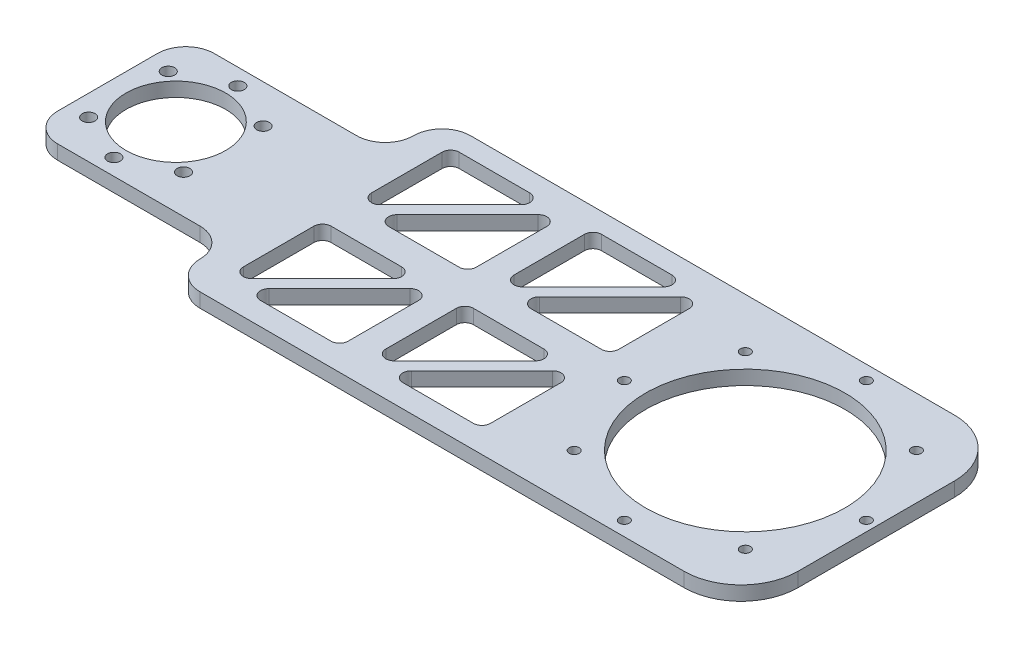
SolidWorks part; units mm, degrees
material "Hexcel AS4C (3000 丝)"
ref_plane "前视基准面" through (0, 0, 0) normal (0, 0, 1) x (1, 0, 0)
ref_plane "上视基准面" through (0, 0, 0) normal (0, 1, 0) x (1, 0, 0)
ref_plane "右视基准面" through (0, 0, 0) normal (1, 0, 0) x (0, 0, -1)
other "Configuration Table"
sketch "草图1" plane through (0, 0, 0) normal (0, 0, 1) x (1, 0, 0)
  line L0 (-270, 0) -> (0, 0)
  dimension "D1" = 270
extrude "拉伸-薄壁1" add sketch "草图1" along normal blind 95 thin thin type one direction wall 5
sketch "草图2" plane through (0, 0, 0) normal (0, 1, 0) x (1, 0, 0)
  line L0 (-241.9416, -47.5) -> (53.3701, -47.5) construction
  line L1 (-270, 0) -> (0, 0) construction
  line L2 (-270, -95) -> (0, -95) construction
  line L3 (0, -95) -> (0, 0) construction
  line L4 (-246, -47.5) -> (-246, 56.1187) construction
  line L5 (-246, -47.5) -> (-229.3385, -33.5194) construction
  circle A0 centre (-246, -47.5) radius 21.75 construction
  circle A1 centre (-46, -47.5) radius 46 construction
  circle A2 centre (-246, -25.75) radius 2.25
  circle A3 centre (-229.3385, -33.5194) radius 2.25
  circle A4 centre (-262.6615, -33.5194) radius 2.25
  circle A5 centre (-262.6615, -61.4806) radius 2.25
  circle A6 centre (-246, -69.25) radius 2.25
  circle A7 centre (-229.3385, -61.4806) radius 2.25
  circle A8 centre (-46, -47.5) radius 42.5 construction
  circle A9 centre (-3.5, -47.5) radius 1.75
  circle A10 centre (-15.948, -77.552) radius 1.75
  circle A11 centre (-46, -90) radius 1.75
  circle A12 centre (-76.052, -77.552) radius 1.75
  circle A13 centre (-88.5, -47.5) radius 1.75
  circle A14 centre (-76.052, -17.448) radius 1.75
  circle A15 centre (-46, -5) radius 1.75
  circle A16 centre (-15.948, -17.448) radius 1.75
  circle A17 centre (-246, -47.5) radius 17.5
  circle A18 centre (-46, -47.5) radius 35
  point P44 (-46, -47.5)
  dimension "D1" = 92
  dimension "D2" = 43.5
  dimension "D4" = 4.5
  dimension "D6" = 85
  dimension "D7" = 3.5
  dimension "D9" = 35
  dimension "D10" = 70
  dimension "D3" = 200
  dimension "D5" = 50
  dimension "D8" = 8
extrude "切除-拉伸1" cut sketch "草图2" against normal blind 10
sketch "草图3" plane through (0, 0, 0) normal (0, 1, 0) x (1, 0, 0)
  line L0 (30.3557, -47.5) -> (-296.2486, -47.5) construction
  line L1 (-270, 0) -> (0, 0) construction
  line L2 (-270, -95) -> (0, -95) construction
  line L3 (-270, -75) -> (-200, -75)
  line L4 (-270, 0) -> (-200, 0)
  line L5 (-270, 0) -> (-270, -20)
  line L6 (-270, -20) -> (-200, -20)
  line L7 (-200, 0) -> (-200, -20)
  line L8 (-200, -95) -> (-200, -75)
  line L9 (-270, -95) -> (-200, -95)
  line L10 (-270, -95) -> (-270, -75)
  line L11 (-190, -10) -> (-190, -34.7574)
  line L12 (-184.8787, -36.8787) -> (-160.1213, -12.1213)
  line L13 (-162.2426, -7) -> (-187, -7)
  line L17 (-154.1213, -12.1213) -> (-178.8787, -36.8787)
  line L18 (-176.7574, -42) -> (-152, -42)
  line L19 (-149, -39) -> (-149, -14.2426)
  line L20 (-112.2426, -7) -> (-137, -7)
  line L21 (-140, -10) -> (-140, -34.7574)
  line L22 (-134.8787, -36.8787) -> (-110.1213, -12.1213)
  line L23 (-99, -39) -> (-99, -14.2426)
  line L24 (-104.1213, -12.1213) -> (-128.8787, -36.8787)
  line L25 (-126.7574, -42) -> (-102, -42)
  line L26 (-112.2426, -52) -> (-137, -52)
  line L27 (-140, -55) -> (-140, -79.7574)
  line L28 (-134.8787, -81.8787) -> (-110.1213, -57.1213)
  line L29 (-99, -84) -> (-99, -59.2426)
  line L30 (-104.1213, -57.1213) -> (-128.8787, -81.8787)
  line L31 (-126.7574, -87) -> (-102, -87)
  line L32 (-162.2426, -52) -> (-187, -52)
  line L33 (-190, -55) -> (-190, -79.7574)
  line L34 (-184.8787, -81.8787) -> (-160.1213, -57.1213)
  line L35 (-149, -84) -> (-149, -59.2426)
  line L36 (-154.1213, -57.1213) -> (-178.8787, -81.8787)
  line L37 (-176.7574, -87) -> (-152, -87)
  arc A0 (-190, -10) -> (-187, -7) centre (-187, -10) cw
  arc A1 (-152, -42) -> (-149, -39) centre (-152, -39) ccw
  arc A2 (-176.7574, -42) -> (-178.8787, -36.8787) centre (-176.7574, -39) cw
  arc A3 (-149, -14.2426) -> (-154.1213, -12.1213) centre (-152, -14.2426) ccw
  arc A4 (-160.1213, -12.1213) -> (-162.2426, -7) centre (-162.2426, -10) ccw
  arc A5 (-184.8787, -36.8787) -> (-190, -34.7574) centre (-187, -34.7574) cw
  arc A6 (-110.1213, -12.1213) -> (-112.2426, -7) centre (-112.2426, -10) ccw
  arc A7 (-140, -10) -> (-137, -7) centre (-137, -10) cw
  arc A8 (-134.8787, -36.8787) -> (-140, -34.7574) centre (-137, -34.7574) cw
  arc A9 (-99, -14.2426) -> (-104.1213, -12.1213) centre (-102, -14.2426) ccw
  arc A10 (-102, -42) -> (-99, -39) centre (-102, -39) ccw
  arc A11 (-126.7574, -42) -> (-128.8787, -36.8787) centre (-126.7574, -39) cw
  arc A12 (-110.1213, -57.1213) -> (-112.2426, -52) centre (-112.2426, -55) ccw
  arc A13 (-140, -55) -> (-137, -52) centre (-137, -55) cw
  arc A14 (-134.8787, -81.8787) -> (-140, -79.7574) centre (-137, -79.7574) cw
  arc A15 (-99, -59.2426) -> (-104.1213, -57.1213) centre (-102, -59.2426) ccw
  arc A16 (-102, -87) -> (-99, -84) centre (-102, -84) ccw
  arc A17 (-126.7574, -87) -> (-128.8787, -81.8787) centre (-126.7574, -84) cw
  arc A18 (-160.1213, -57.1213) -> (-162.2426, -52) centre (-162.2426, -55) ccw
  arc A19 (-190, -55) -> (-187, -52) centre (-187, -55) cw
  arc A20 (-184.8787, -81.8787) -> (-190, -79.7574) centre (-187, -79.7574) cw
  arc A21 (-149, -59.2426) -> (-154.1213, -57.1213) centre (-152, -59.2426) ccw
  arc A22 (-152, -87) -> (-149, -84) centre (-152, -84) ccw
  arc A23 (-176.7574, -87) -> (-178.8787, -81.8787) centre (-176.7574, -84) cw
  point P20 (-190, -7)
  point P29 (-149, -42)
  point P32 (-184, -42)
  point P35 (-149, -7)
  point P38 (-155, -7)
  point P41 (-190, -42)
  dimension "D10" = 3
  dimension "D1" = 20
  dimension "D2" = 70
  dimension "D3" = 35
  dimension "D4" = 35
  dimension "D5" = 7
  dimension "D6" = 10
  dimension "D7" = 35
  dimension "D8" = 35
  dimension "D9" = 6
  dimension "D13" = 9
  dimension "D14" = 10
  dimension "D11" = 2
  dimension "D12" = 2
extrude "切除-拉伸2" cut sketch "草图3" against normal blind 10
fillet "圆角1" radius 10 6 edges at (-200, -2.5, 95) (-200, -2.5, 0) (-200, -2.5, 20) (-200, -2.5, 75) (-270, -2.5, 75) (-270, -2.5, 20)
fillet "圆角2" radius 20 2 edges at (0, -2.5, 95) (0, -2.5, 0)
